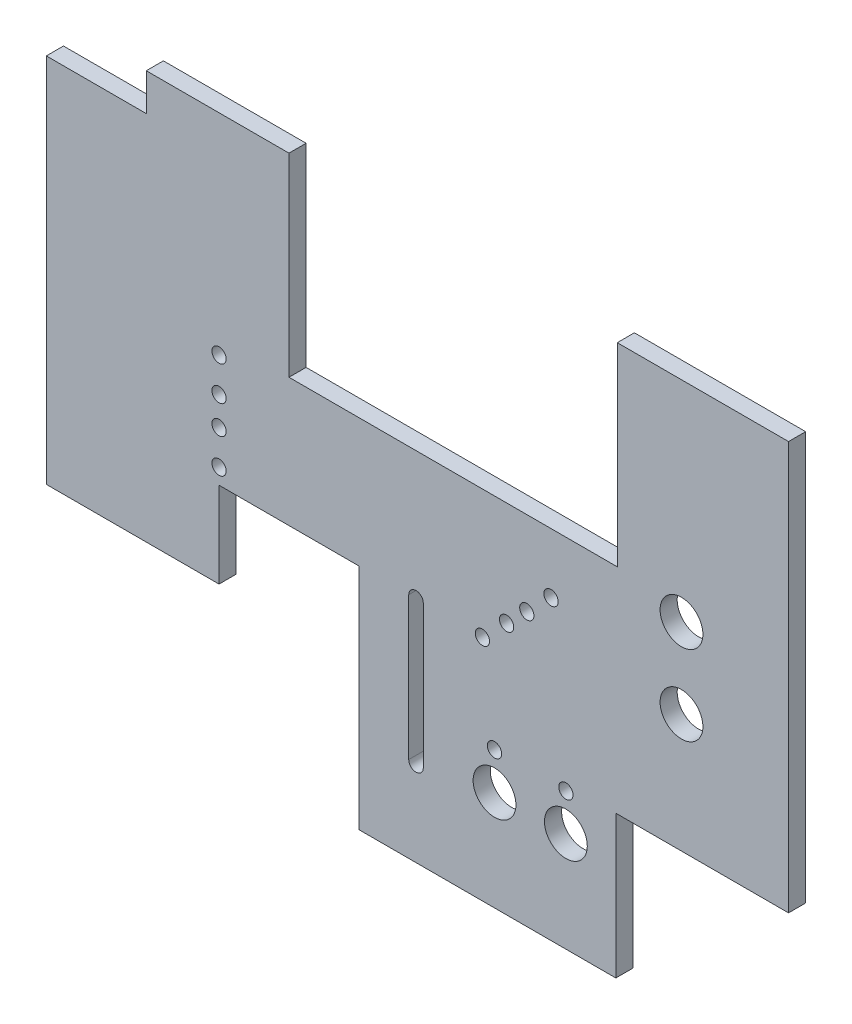
SolidWorks part; units mm, degrees
material "MDF"
ref_plane "Plano frontal" through (0, 0, 0) normal (0, 0, 1) x (1, 0, 0)
ref_plane "Plano superior" through (0, 0, 0) normal (0, 1, 0) x (1, 0, 0)
ref_plane "Plano direito" through (0, 0, 0) normal (1, 0, 0) x (0, 0, -1)
sketch "Esboço1" plane through (0, 0, 0) normal (0, 0, 1) x (1, 0, 0)
  line L0 (-45, 96.5) -> (-45, 28.5)
  line L1 (-130, -96.5) -> (130, -96.5)
  line L2 (-130, -96.5) -> (-130, 96.5)
  line L3 (-130, 96.5) -> (130, 96.5)
  line L4 (130, -96.5) -> (130, 96.5)
  line L5 (-130, -96.5) -> (130, 96.5) construction
  line L6 (-130, 96.5) -> (130, -96.5) construction
  line L7 (-45, 28.5) -> (70, 28.5)
  line L8 (-69.5, -16.5) -> (-20.5, -16.5)
  line L9 (-20.5, -16.5) -> (-20.5, -96.5)
  line L10 (0, 0) -> (0, 96.5) construction
  line L11 (69.5, -146.5) -> (69.5, -46.5)
  line L12 (69.5, -46.5) -> (130, -46.5)
  line L13 (70, 96.5) -> (70, 28.5)
  line L14 (-130, 83.5) -> (-95, 83.5)
  line L15 (-95, 83.5) -> (-95, 96.5)
  line L16 (-69.5, -16.5) -> (-69.5, -46.5)
  line L17 (-69.5, -46.5) -> (-130, -46.5)
  line L18 (-0.5, -66.5) -> (-0.5, -16.5) construction
  line L19 (-3.05, -66.5) -> (-3.05, -16.5)
  line L20 (2.05, -66.5) -> (2.05, -16.5)
  line L21 (-20.5, -41.5) -> (19.5, -41.5) construction
  line L22 (27, -61.5) -> (52, -61.5) construction
  line L23 (22.7574, -16.5) -> (31.2426, -8.0147) construction
  line L24 (31.2426, -8.0147) -> (38.3137, -0.9437) construction
  line L25 (38.3137, -0.9437) -> (46.799, 7.5416) construction
  line L26 (-69.5, 23) -> (-69.5, 11) construction
  line L27 (-69.5, 11) -> (-69.5, 1) construction
  line L28 (-69.5, 1) -> (-69.5, -11) construction
  line L29 (-99.5, 28.5) -> (-99.5, -13.5) construction
  line L33 (-115.8616, -46.3857) -> (-130, -46.3857) construction
  line L34 (-115.8616, -46.3857) -> (-115.8616, -28.9225) construction
  line L35 (-115.8616, -28.9225) -> (-130, -28.9225) construction
  line L36 (-130, -46.3857) -> (-130, -28.9225) construction
  line L37 (-122.9308, -28.9225) -> (-122.9308, -46.3857) construction
  line L38 (-115.8616, -37.6541) -> (-130, -37.6541) construction
  arc A0 (-3.05, -66.5) -> (2.05, -66.5) centre (-0.5, -66.5) ccw
  arc A1 (2.05, -16.5) -> (-3.05, -16.5) centre (-0.5, -16.5) ccw
  circle A3 centre (27, -61.5) radius 7.5
  circle A4 centre (92.5, -5) radius 7.5
  circle A5 centre (92.5, 23) radius 7.5
  circle A6 centre (-69.5, -11) radius 2.5
  circle A7 centre (-69.5, 1) radius 2.5
  circle A8 centre (-69.5, 11) radius 2.5
  circle A9 centre (-69.5, 23) radius 2.5
  circle A10 centre (22.7574, -16.5) radius 2.5
  circle A11 centre (31.2426, -8.0147) radius 2.5
  circle A12 centre (38.3137, -0.9437) radius 2.5
  circle A13 centre (46.799, 7.5416) radius 2.5
  circle A14 centre (52, -61.5) radius 7.5
  circle A19 centre (52, -48.5) radius 2.5
  circle A20 centre (27, -48.5) radius 2.5
  point P0 (0, 0)
  point P25 (-0.5, -41.5)
  point P36 (19.5, -61.5)
  point P37 (42.5563, 3.299)
  point P42 (92.5, 15.5)
  point P43 (92.5, 2.5)
  point P44 (92.5, 15.5)
  point P45 (85, 23)
  point P46 (92.5, -12.5)
  point P55 (-69.5, 25.5)
  point P56 (-69.5, -13.5)
  point P67 (27, -12.2574)
  point P70 (0, 0)
  point P71 (0, 0)
  point P74 (0, 0)
  point P75 (27, -48.5)
  point P84 (-122.9308, -37.6541)
  dimension "D13" = 2.55
  dimension "D17" = 15
  dimension "D20" = 15
  dimension "D21" = 13
  dimension "D23" = 45
  dimension "D24" = 5
  dimension "D25" = 12
  dimension "D18" = 45
  dimension "D31" = 13
  dimension "D1" = 260
  dimension "D2" = 50
  dimension "D3" = 125
  dimension "D4" = 85
  dimension "D5" = 193
  dimension "D6" = 100
  dimension "D7" = 60.5
  dimension "D8" = 90
  dimension "D9" = 80
  dimension "D10" = 60
  dimension "D11" = 35
  dimension "D12" = 180
  dimension "D14" = 50
  dimension "D15" = 20
  dimension "D16" = 30
  dimension "D19" = 25
  dimension "D22" = 13
  dimension "D26" = 3
  dimension "D27" = 3
  dimension "D28" = 12
  dimension "D29" = 30
  dimension "D30" = 35
extrude "Ressalto-extrusão1" add sketch "Esboço1" along normal blind 6 contours L3 L7 L0 L2 L1 L11 L12 L4 region at (2.7473, 5.0762, 0)
